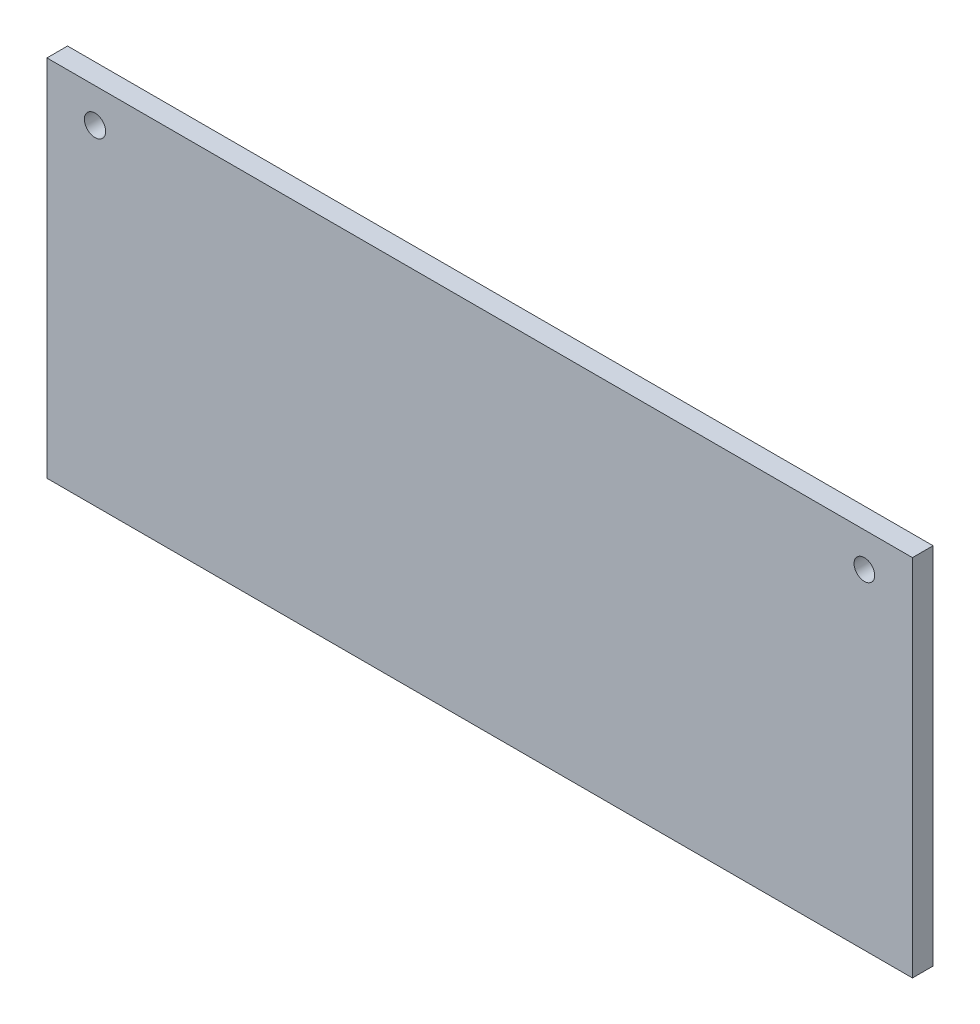
SolidWorks part; units mm, degrees
ref_plane "前视基准面" through (0, 0, 0) normal (0, 0, 1) x (1, 0, 0)
ref_plane "上视基准面" through (0, 0, 0) normal (0, 1, 0) x (1, 0, 0)
ref_plane "右视基准面" through (0, 0, 0) normal (1, 0, 0) x (0, 0, -1)
other "Configuration Table"
sketch "草图1" plane through (0, 0, 0) normal (0, 0, 1) x (1, 0, 0)
  line L1 (63, -26.5) -> (-63, -26.5)
  line L2 (63, -26.5) -> (63, 26.5)
  line L3 (63, 26.5) -> (-63, 26.5)
  line L4 (-63, -26.5) -> (-63, 26.5)
  line L5 (63, -26.5) -> (-63, 26.5) construction
  line L6 (63, 26.5) -> (-63, -26.5) construction
  point P0 (0, 0)
  dimension "D1" = 126
  dimension "D2" = 53
extrude "凸台-拉伸1" add sketch "草图1" along normal blind 3
sketch "草图2" plane through (0, 0, 0) normal (0, 0, -1) x (-1, 0, 0)
  line L0 (-63, 26.5) -> (63, 26.5) construction
  line L1 (-63, -26.5) -> (-63, 26.5) construction
  line L2 (63, 26.5) -> (63, -26.5) construction
  circle A0 centre (56, 21.5) radius 1.55
  circle A1 centre (-56, 21.5) radius 1.5
  dimension "D1" = 5
  dimension "D2" = 5
  dimension "D3" = 7
  dimension "D4" = 7
extrude "切除-拉伸1" cut sketch "草图2" against normal blind 10 contours A0 | A1
